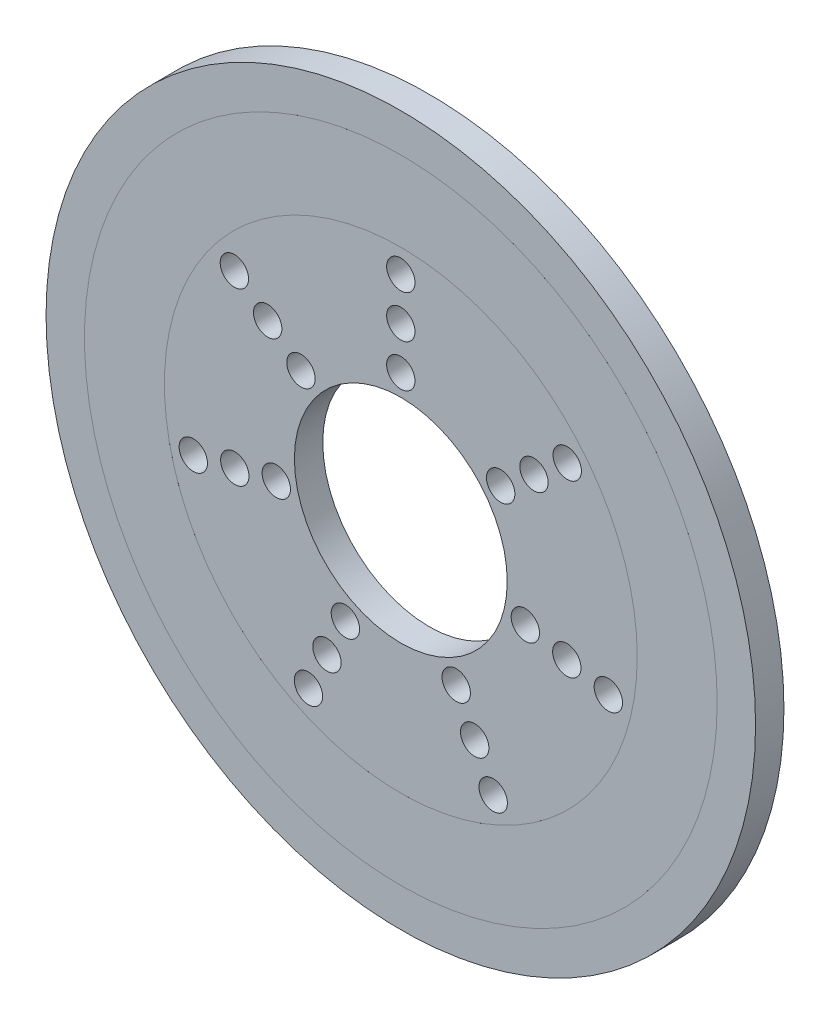
SolidWorks part; units mm, degrees
ref_plane "Front Plane" through (0, 0, 0) normal (0, 0, 1) x (1, 0, 0)
ref_plane "Top Plane" through (0, 0, 0) normal (0, 1, 0) x (1, 0, 0)
ref_plane "Right Plane" through (0, 0, 0) normal (1, 0, 0) x (0, 0, -1)
sketch "Sketch1" plane through (0, 0, 0) normal (0, 0, 1) x (1, 0, 0)
  circle A0 centre (0, 0) radius 125
  circle A1 centre (0, 0) radius 37.5
  circle A2 centre (0, 45) radius 5
  circle A3 centre (0, 60) radius 5
  circle A4 centre (0, 75) radius 5
  circle A5 centre (0, 90) radius 5
  circle A6 centre (0, 105) radius 5
  circle A13 centre (82.0923, 65.4664) radius 5
  circle A14 centre (70.3648, 56.1141) radius 5
  circle A15 centre (58.6374, 46.7617) radius 5
  circle A16 centre (46.9099, 37.4094) radius 5
  circle A17 centre (35.1824, 28.057) radius 5
  circle A20 centre (102.3674, -23.3647) radius 5
  circle A21 centre (87.7435, -20.0269) radius 5
  circle A22 centre (73.1196, -16.6891) radius 5
  circle A23 centre (58.4957, -13.3513) radius 5
  circle A24 centre (43.8718, -10.0134) radius 5
  circle A27 centre (45.5578, -94.6017) radius 5
  circle A28 centre (39.0495, -81.0872) radius 5
  circle A29 centre (32.5413, -67.5727) radius 5
  circle A30 centre (26.033, -54.0581) radius 5
  circle A31 centre (19.5248, -40.5436) radius 5
  circle A34 centre (-45.5578, -94.6017) radius 5
  circle A35 centre (-39.0495, -81.0872) radius 5
  circle A36 centre (-32.5413, -67.5727) radius 5
  circle A37 centre (-26.033, -54.0581) radius 5
  circle A38 centre (-19.5248, -40.5436) radius 5
  circle A41 centre (-102.3674, -23.3647) radius 5
  circle A42 centre (-87.7435, -20.0269) radius 5
  circle A43 centre (-73.1196, -16.6891) radius 5
  circle A44 centre (-58.4957, -13.3513) radius 5
  circle A45 centre (-43.8718, -10.0134) radius 5
  circle A48 centre (-82.0923, 65.4664) radius 5
  circle A49 centre (-70.3648, 56.1141) radius 5
  circle A50 centre (-58.6374, 46.7617) radius 5
  circle A51 centre (-46.9099, 37.4094) radius 5
  circle A52 centre (-35.1824, 28.057) radius 5
  point P104 (0, 0)
  dimension "D1" = 45
  dimension "D2" = 250
  dimension "D3" = 75
  dimension "D5" = 10
  dimension "D4" = 5
  dimension "D6" = 7
extrude "Boss-Extrude2" add sketch "Sketch1" along normal blind 10
sketch "Sketch2" plane through (0, 0, 10) normal (0, 0, 1) x (1, 0, 0)
  circle A0 centre (0, 0) radius 83.3036
  circle A1 centre (0, 0) radius 111.469
extrude "Boss-Extrude3" add sketch "Sketch2" against normal blind 10.001
extrude "Boss-Extrude4" add sketch "Sketch2<2>" along normal blind 0.001
sketch "Sketch2<2>" plane through (0, 0, 10) normal (0, 0, 1) x (1, 0, 0) same geometry as "Sketch2"
